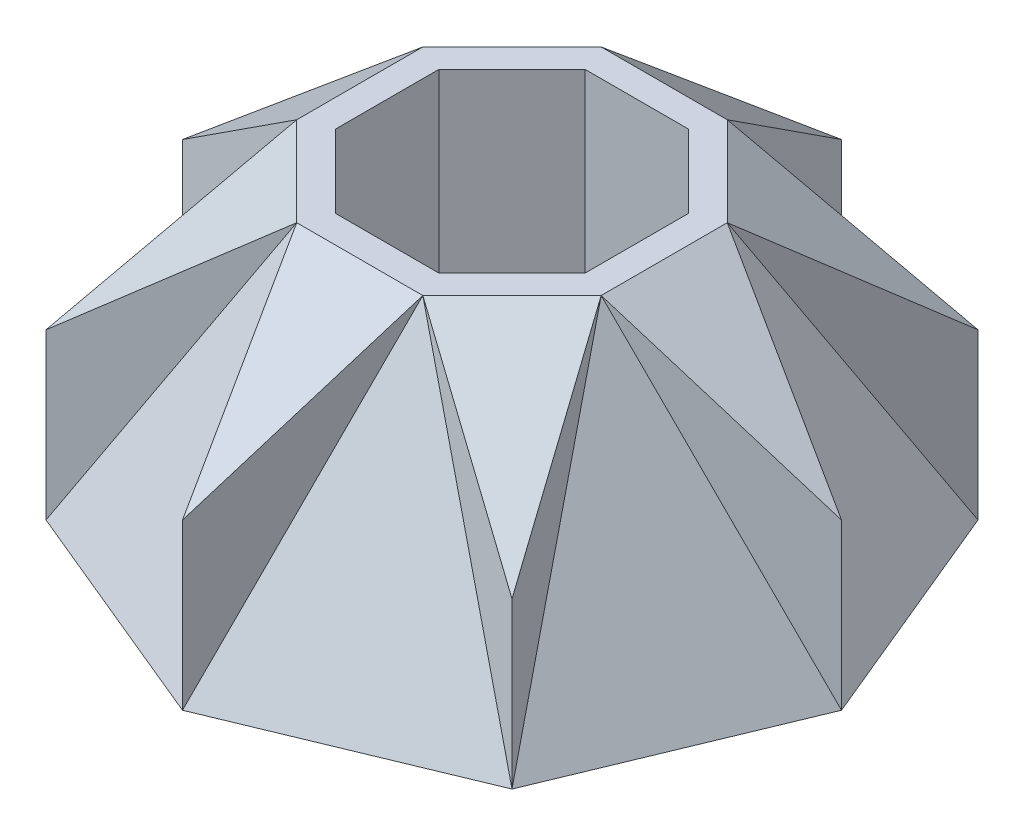
SolidWorks part; units mm, degrees
ref_plane "前视基准面" through (0, 0, 0) normal (0, 0, 1) x (1, 0, 0)
ref_plane "上视基准面" through (0, 0, 0) normal (0, 1, 0) x (1, 0, 0)
ref_plane "右视基准面" through (0, 0, 0) normal (1, 0, 0) x (0, 0, -1)
other "Configuration Table"
sketch "草图1" plane through (0, 0, 0) normal (0, 1, 0) x (1, 0, 0)
  line L0 (-9.4094, -22.7164) -> (9.4094, -22.7164)
  line L1 (60, 0) -> (42.4264, 42.4264)
  line L2 (42.4264, 42.4264) -> (0, 60)
  line L3 (0, 60) -> (-42.4264, 42.4264)
  line L4 (-42.4264, 42.4264) -> (-60, 0)
  line L5 (-60, 0) -> (-42.4264, -42.4264)
  line L6 (-42.4264, -42.4264) -> (0, -60)
  line L7 (0, -60) -> (42.4264, -42.4264)
  line L8 (42.4264, -42.4264) -> (60, 0)
  line L9 (27.7164, -11.4805) -> (27.7164, 11.4805)
  line L10 (27.7164, 11.4805) -> (11.4805, 27.7164)
  line L11 (11.4805, 27.7164) -> (-11.4805, 27.7164)
  line L12 (-11.4805, 27.7164) -> (-27.7164, 11.4805)
  line L13 (-27.7164, 11.4805) -> (-27.7164, -11.4805)
  line L14 (-27.7164, -11.4805) -> (-11.4805, -27.7164)
  line L15 (-11.4805, -27.7164) -> (11.4805, -27.7164)
  line L16 (11.4805, -27.7164) -> (27.7164, -11.4805)
  line L17 (9.4094, -22.7164) -> (22.7164, -9.4094)
  line L18 (22.7164, -9.4094) -> (22.7164, 9.4094)
  line L19 (22.7164, 9.4094) -> (9.4094, 22.7164)
  line L20 (9.4094, 22.7164) -> (-9.4094, 22.7164)
  line L21 (-9.4094, 22.7164) -> (-22.7164, 9.4094)
  line L22 (-22.7164, 9.4094) -> (-22.7164, -9.4094)
  line L23 (-22.7164, -9.4094) -> (-9.4094, -22.7164)
  circle A0 centre (0, 0) radius 55.4328 construction
  circle A1 centre (0, 0) radius 27.7164 construction
  dimension "D1" = 120
  dimension "D2" = 60
  dimension "D3" = 5
extrude "凸台-拉伸1" add sketch "草图1" against normal blind 55 contours L7 L8 L1 L2 L3 L4 L5 L6 L16 L15 L14 L13 L12 L11 L10 L9 | L15 L16 L9 L10 L11 L12 L13 L14 L23 L22 L21 L20 L19 L18 L17 L0 region at (49.6453, 0, 20.5638) region at (19.0441, 0, 19.0441)
ref_axis "基准轴1" through (0, 57.75, 0) along (0, -1, 0)
ref_plane "基准面1" through (9.4581, 11.4287, 22.8339) normal (0.3473, 0.4197, 0.8386) x (0.9377, -0.1555, -0.3106)
sketch "草图2" plane through (9.4581, 11.4287, 22.8339) normal (0.3473, 0.4197, 0.8386) x (0.9377, -0.1555, -0.3106)
  line L1 (126.6969, -162.0609) -> (-110.4533, -162.0609)
  line L2 (126.6969, -162.0609) -> (126.6969, 64.4441)
  line L3 (126.6969, 64.4441) -> (-110.4533, 64.4441)
  line L4 (-110.4533, -162.0609) -> (-110.4533, 64.4441)
  line L5 (126.6969, -162.0609) -> (-110.4533, 64.4441) construction
  line L6 (126.6969, 64.4441) -> (-110.4533, -162.0609) construction
  point P0 (8.1218, -48.8084)
extrude "切除-拉伸2" cut sketch "草图2" along normal blind 50
pattern_circular "阵列(圆周)1" count 8 over 360 about axis through (0, 57.75, 0) along (0, -1, 0) of "切除-拉伸2"
ref_plane "基准面2" through (0, -25, 0) normal (0, 1, 0) x (1, 0, 0)
sketch "草图3" plane through (0, -25, 0) normal (0, 1, 0) x (1, 0, 0)
  point P0 (-60, 0)
ref_plane "基准面3" through (-10.3901, 13.4172, 0) normal (0.6123, -0.7906, 0) x (-0.7906, -0.6123, 0)
sketch "草图4" plane through (-10.3901, 13.4172, 0) normal (0.6123, -0.7906, 0) x (-0.7906, -0.6123, 0)
  line L0 (62.7457, 0) -> (21.914, -11.4805)
  line L1 (21.914, -11.4805) -> (21.914, 11.4805)
  line L2 (21.914, 11.4805) -> (62.7457, 0)
extrude "切除-拉伸4" cut sketch "草图4" against normal blind 50
sketch "草图5" plane through (-10.3901, 13.4172, 0) normal (0.6123, -0.7906, 0) x (-0.7906, -0.6123, 0)
  line L0 (62.7457, 0) -> (21.914, -11.4805)
  line L1 (21.914, -11.4805) -> (21.914, 11.4805)
  line L2 (21.914, 11.4805) -> (62.7457, 0)
sketch "草图6" plane through (0, -55, 0) normal (0, -1, 0) x (1, 0, 0)
  line L0 (-60, 0) -> (-27.7164, 11.4805)
  line L1 (-27.7164, 11.4805) -> (-27.7164, -11.4805)
  line L2 (-27.7164, -11.4805) -> (-60, 0)
loft "放样1" add profiles "草图6", "草图5"
pattern_circular "阵列(圆周)2" count 8 every 45 about axis through (0, 57.75, 0) along (0, -1, 0) of "放样1"
pattern_circular "阵列(圆周)3" count 8 every 45 about axis through (0, 57.75, 0) along (0, -1, 0) of "切除-拉伸4"
